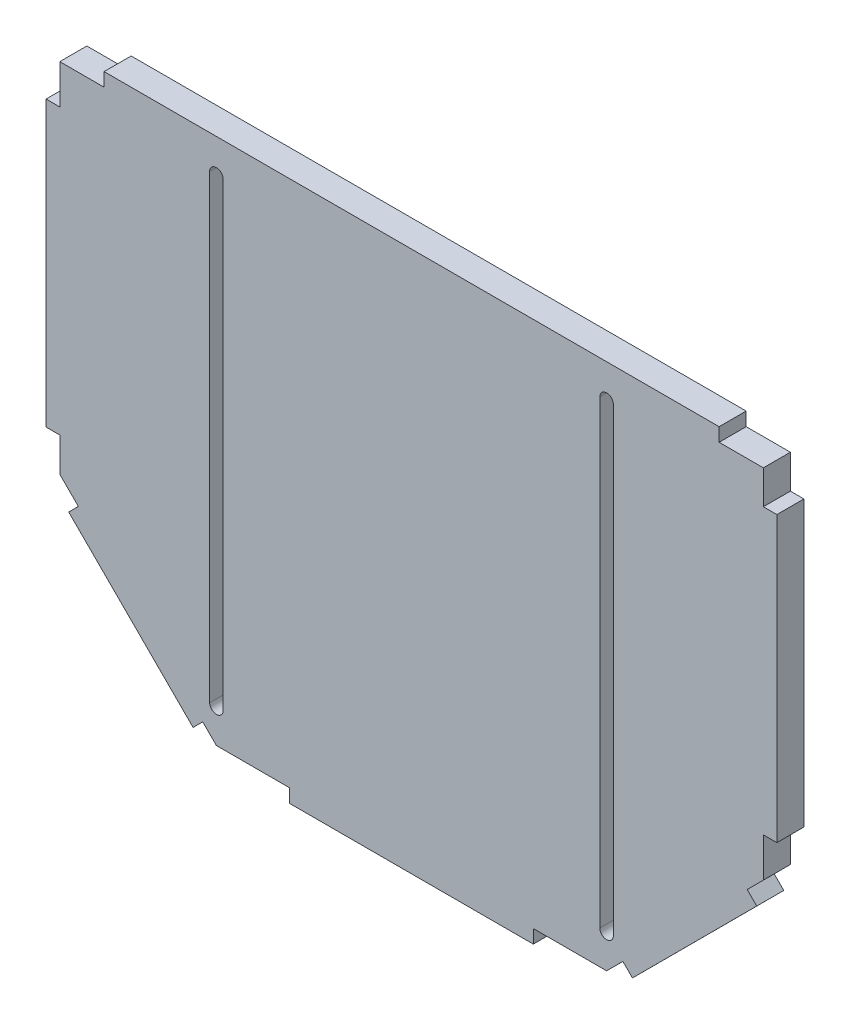
SolidWorks part; units mm, degrees
ref_plane "Front Plane" through (0, 0, 0) normal (0, 0, 1) x (1, 0, 0)
ref_plane "Top Plane" through (0, 0, 0) normal (0, 1, 0) x (1, 0, 0)
ref_plane "Right Plane" through (0, 0, 0) normal (1, 0, 0) x (0, 0, -1)
sketch "Sketch2" plane through (0, 0, 0) normal (0, 0, 1) x (1, 0, 0)
  line L0 (0.1651, 2.5942) -> (34.5821, 2.5942)
  line L1 (183.2991, 2.5942) -> (190.9281, 10.2317)
  line L2 (256.8547, 76.2323) -> (256.8547, 94.6473)
  line L3 (256.8547, 243.8181) -> (236.1007, 243.8181)
  line L4 (-73.3453, 243.8181) -> (-73.3453, 225.4031)
  line L5 (-73.3453, 76.1046) -> (-64.6252, 67.3845)
  line L6 (195.4207, 5.744) -> (253.7596, 64.1484)
  line L7 (34.5821, -3.7558) -> (148.8821, -3.7558)
  line L8 (34.5821, -3.7558) -> (34.5821, 2.5942)
  line L10 (148.8821, -3.7558) -> (148.8821, 2.5942)
  line L11 (-52.5463, 243.8181) -> (-73.3453, 243.8181)
  line L13 (195.4207, 5.744) -> (190.9281, 10.2317)
  line L14 (253.7596, 64.1484) -> (249.267, 68.636)
  line L15 (256.8547, 227.9973) -> (256.8547, 243.8181)
  line L16 (263.2047, 227.9973) -> (256.8547, 227.9973)
  line L17 (263.2047, 227.9973) -> (263.2047, 94.6473)
  line L18 (263.2047, 94.6473) -> (256.8547, 94.6473)
  line L20 (249.267, 68.636) -> (256.8547, 76.2323)
  line L21 (-6.2536, 9.0129) -> (0.1651, 2.5942)
  line L22 (148.8821, 2.5942) -> (183.2991, 2.5942)
  line L23 (-79.7779, 225.4031) -> (-73.3453, 225.4031)
  line L24 (-79.7779, 225.4031) -> (-79.7779, 92.0531)
  line L25 (-79.7779, 92.0531) -> (-73.3453, 92.0531)
  line L26 (-69.1567, 62.8531) -> (-64.6252, 67.3845)
  line L27 (-10.785, 4.4814) -> (-6.2536, 9.0129)
  line L28 (-10.785, 4.4814) -> (-69.1567, 62.8531)
  line L29 (-73.3453, 92.0531) -> (-73.3453, 76.1046)
  line L30 (-52.5463, 243.8181) -> (-52.5463, 250.1681)
  line L31 (-52.5463, 250.1681) -> (236.1007, 250.1681)
  line L32 (236.1007, 243.8181) -> (236.1007, 250.1681)
  line L35 (-14.0237, 16.783) -> (-73.3453, 76.1046) construction
  line L36 (0.1651, 2.5942) -> (-14.0237, 16.783) construction
  dimension "D2" = 183.134
  dimension "D5" = 6.35
  dimension "D6" = 114.3
  dimension "D7" = 34.417
  dimension "D8" = 6.35
  dimension "D9" = 82.55
  dimension "D10" = 10.795
  dimension "D11" = 6.35
  dimension "D12" = 133.35
  dimension "D13" = 18.415
extrude "Boss-Extrude1" add sketch "Sketch2" along normal blind 12.7
sketch "Sketch3" plane through (0, 0, 12.7) normal (0, 0, 1) x (1, 0, 0)
  line L0 (0.1651, 2.5942) -> (0.1651, 250.1681) construction
  line L1 (236.1007, 250.1681) -> (-52.5463, 250.1681) construction
  line L3 (183.2991, 2.5942) -> (183.2991, 250.1681) construction
  line L6 (-3.0099, 234.3311) -> (-3.0099, 18.4311)
  line L8 (3.3401, 234.3311) -> (3.3401, 18.4311)
  line L10 (180.1241, 234.3311) -> (180.1241, 18.4311)
  line L12 (186.4741, 234.3311) -> (186.4741, 18.4311)
  arc A0 (-3.0099, 234.3311) -> (3.3401, 234.3311) centre (0.1651, 234.3311) cw
  arc A1 (180.1241, 234.3311) -> (186.4741, 234.3311) centre (183.2991, 234.3311) cw
  arc A2 (-3.0099, 18.4311) -> (3.3401, 18.4311) centre (0.1651, 18.4311) ccw
  arc A3 (180.1241, 18.4311) -> (186.4741, 18.4311) centre (183.2991, 18.4311) ccw
  point P13 (-3.0099, 126.3811)
  point P14 (0.1651, 126.3811)
  point P20 (186.4741, 126.3811)
  point P21 (183.2991, 126.3811)
  dimension "D1" = 215.9
  dimension "D2" = 6.35
  dimension "D3" = 6.35
  dimension "D4" = 215.9
extrude "Cut-Extrude1" cut sketch "Sketch3" against normal blind 6.35
